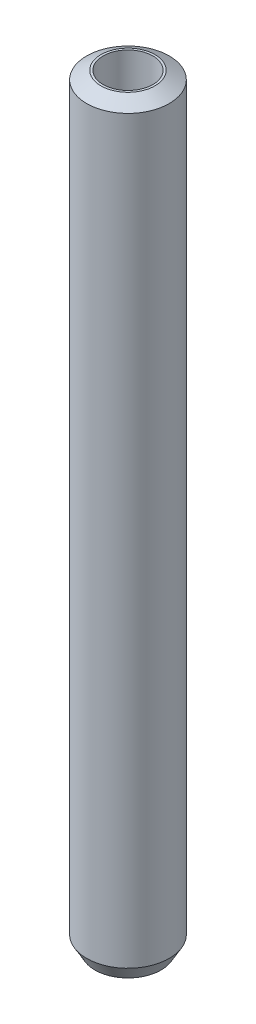
SolidWorks part; units mm, degrees
ref_plane "Front Plane" through (0, 0, 0) normal (0, 0, 1) x (1, 0, 0)
ref_plane "Top Plane" through (0, 0, 0) normal (0, 1, 0) x (1, 0, 0)
ref_plane "Right Plane" through (0, 0, 0) normal (1, 0, 0) x (0, 0, -1)
sketch "Sketch1" plane through (0, 0, 0) normal (0, 1, 0) x (1, 0, 0)
  circle A0 centre (0, 0) radius 17.5
  dimension "SHAFT_OD" = 35
extrude "Boss-Extrude1" add sketch "Sketch1" along normal blind 323.3055
sketch "Sketch2" plane through (0, 0, 0) normal (0, 1, 0) x (1, 0, 0)
  circle A0 centre (0, 0) radius 10.5338
  dimension "BORE_D" = 21.0675
extrude "Cut-Extrude1" cut sketch "Sketch2" along normal through all
chamfer "Chamfer1" distance 3.483 angle 60 2 edges at (0, 323.3055, 17.5) (0, 0, 17.5) first distance on face at (0, 323.3055, 17.5) first distance on face at (0, 0, 10.5338)
